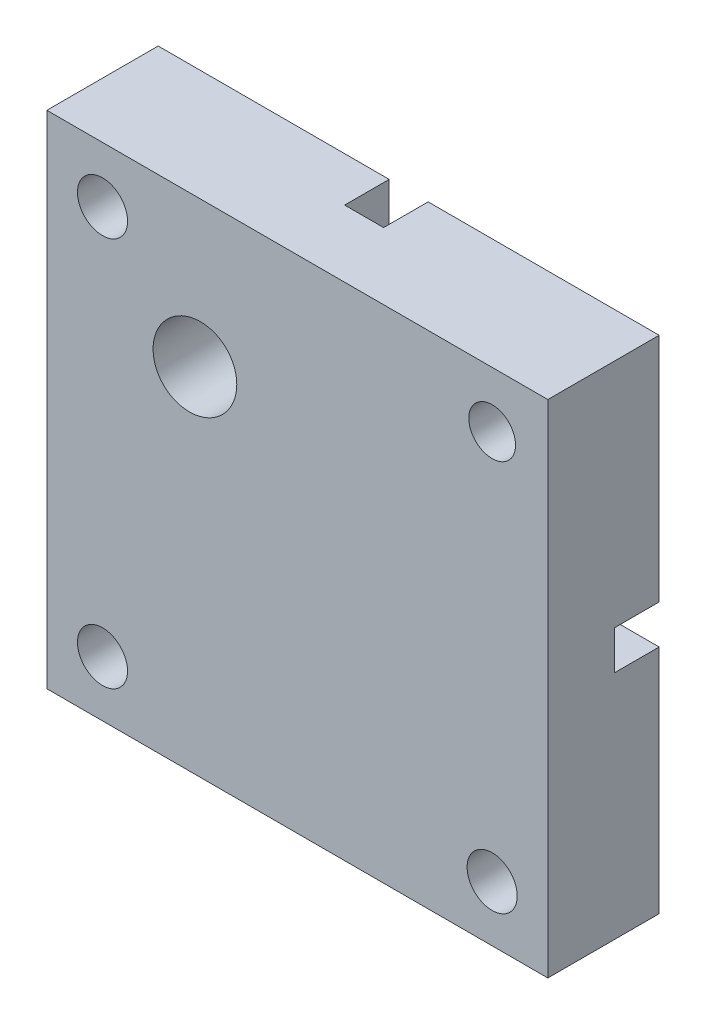
SolidWorks part; units mm, degrees
ref_plane "Front Plane" through (0, 0, 0) normal (0, 0, 1) x (1, 0, 0)
ref_plane "Top Plane" through (0, 0, 0) normal (0, 1, 0) x (1, 0, 0)
ref_plane "Right Plane" through (0, 0, 0) normal (1, 0, 0) x (0, 0, -1)
sketch "Sketch1" plane through (0, 0, 0) normal (0, 0, 1) x (1, 0, 0)
  line L0 (16.1302, 34.5266) -> (10.4734, 28.8698) construction
  line L1 (0, 0) -> (45, 0)
  line L2 (0, 0) -> (0, 45)
  line L3 (0, 45) -> (45, 45)
  line L4 (45, 0) -> (45, 45)
  line L5 (5, 5) -> (40, 5) construction
  line L6 (5, 5) -> (5, 40) construction
  line L7 (5, 40) -> (40, 40) construction
  line L8 (40, 5) -> (40, 40) construction
  line L9 (5, 5) -> (40, 40) construction
  line L10 (5, 40) -> (40, 5) construction
  line L11 (8.1754, 40) -> (6.5877, 42.75) construction
  line L12 (6.5877, 42.75) -> (3.4123, 42.75) construction
  line L13 (3.4123, 42.75) -> (1.8246, 40) construction
  line L14 (1.8246, 40) -> (3.4123, 37.25) construction
  line L15 (3.4123, 37.25) -> (6.5877, 37.25) construction
  line L16 (6.5877, 37.25) -> (8.1754, 40) construction
  circle A0 centre (5, 5) radius 2.25
  circle A1 centre (5, 40) radius 2.25
  circle A2 centre (40, 40) radius 2.1
  circle A3 centre (40, 5) radius 2.25
  circle A4 centre (5, 40) radius 2.75 construction
  ellipse E0 centre (13.3018, 31.6982) end of major axis (16.1302, 34.5266) minor radius 3.5
  point P10 (22.5, 22.5)
  point P22 (11.6648, 33.3352)
  point P28 (13.8865, 31.1135)
  point P31 (13.3018, 31.6982)
  dimension "D3" = 4.5
  dimension "D4" = 4.5
  dimension "D5" = 4.2
  dimension "D6" = 4.5
  dimension "D1" = 45
  dimension "D2" = 45
  dimension "D7" = 5
  dimension "D8" = 5
  dimension "D9" = 5
  dimension "D10" = 5
  dimension "D11" = 5.5
  dimension "D12" = 135
  dimension "D13" = 8
  dimension "D14" = 7
extrude "Boss-Extrude1" add sketch "Sketch1" along normal blind 10
sketch "Sketch2" plane through (0, 0, 0) normal (0, 0, 1) x (1, 0, 0)
  line L1 (8.7528, 5) -> (6.8764, 8.25)
  line L2 (6.8764, 8.25) -> (3.1236, 8.25)
  line L3 (3.1236, 8.25) -> (1.2472, 5)
  line L4 (1.2472, 5) -> (3.1236, 1.75)
  line L5 (3.1236, 1.75) -> (6.8764, 1.75)
  line L6 (6.8764, 1.75) -> (8.7528, 5)
  line L7 (8.7528, 40) -> (6.8764, 43.25)
  line L8 (6.8764, 43.25) -> (3.1236, 43.25)
  line L9 (3.1236, 43.25) -> (1.2472, 40)
  line L10 (1.2472, 40) -> (3.1236, 36.75)
  line L11 (3.1236, 36.75) -> (6.8764, 36.75)
  line L12 (6.8764, 36.75) -> (8.7528, 40)
  line L13 (43.7528, 40) -> (41.8764, 43.25)
  line L14 (41.8764, 43.25) -> (38.1236, 43.25)
  line L15 (38.1236, 43.25) -> (36.2472, 40)
  line L16 (36.2472, 40) -> (38.1236, 36.75)
  line L17 (38.1236, 36.75) -> (41.8764, 36.75)
  line L18 (41.8764, 36.75) -> (43.7528, 40)
  line L19 (43.7528, 5) -> (41.8764, 8.25)
  line L20 (41.8764, 8.25) -> (38.1236, 8.25)
  line L21 (38.1236, 8.25) -> (36.2472, 5)
  line L22 (36.2472, 5) -> (38.1236, 1.75)
  line L23 (38.1236, 1.75) -> (41.8764, 1.75)
  line L24 (41.8764, 1.75) -> (43.7528, 5)
  circle A0 centre (5, 5) radius 3.25 construction
  circle A1 centre (5, 40) radius 3.25 construction
  circle A2 centre (40, 40) radius 3.25 construction
  circle A3 centre (40, 5) radius 3.25 construction
  dimension "D1" = 6.5
  dimension "D2" = 6.5
  dimension "D3" = 6.5
  dimension "D4" = 6.5
extrude "Cut-Extrude1" cut sketch "Sketch2" along normal blind 5
sketch "Sketch3" plane through (0, 0, 0) normal (0, 0, -1) x (-1, 0, 0)
  line L0 (-45, 24.25) -> (-24.25, 24.25)
  line L1 (-45, 0) -> (-45, 45) construction
  line L2 (-24.25, 24.25) -> (-24.25, 45)
  line L3 (-45, 45) -> (0, 45) construction
  line L4 (-24.25, 45) -> (-20.75, 45)
  line L5 (-20.75, 45) -> (-20.75, 24.25)
  line L6 (-20.75, 24.25) -> (0, 24.25)
  line L7 (0, 45) -> (0, 0) construction
  line L8 (0, 24.25) -> (0, 20.75)
  line L9 (0, 20.75) -> (-20.75, 20.75)
  line L10 (-20.75, 20.75) -> (-20.75, 0)
  line L11 (0, 0) -> (-45, 0) construction
  line L12 (-20.75, 0) -> (-24.25, 0)
  line L13 (-24.25, 0) -> (-24.25, 20.75)
  line L14 (-24.25, 20.75) -> (-45, 20.75)
  line L15 (-45, 20.75) -> (-45, 24.25)
  point P12 (-22.5, 0)
  point P21 (-22.5, 0)
  point P22 (-45, 22.5)
  point P24 (-45, 22.5)
  dimension "D1" = 3.5
  dimension "D2" = 3.5
extrude "Cut-Extrude2" cut sketch "Sketch3" against normal blind 4
